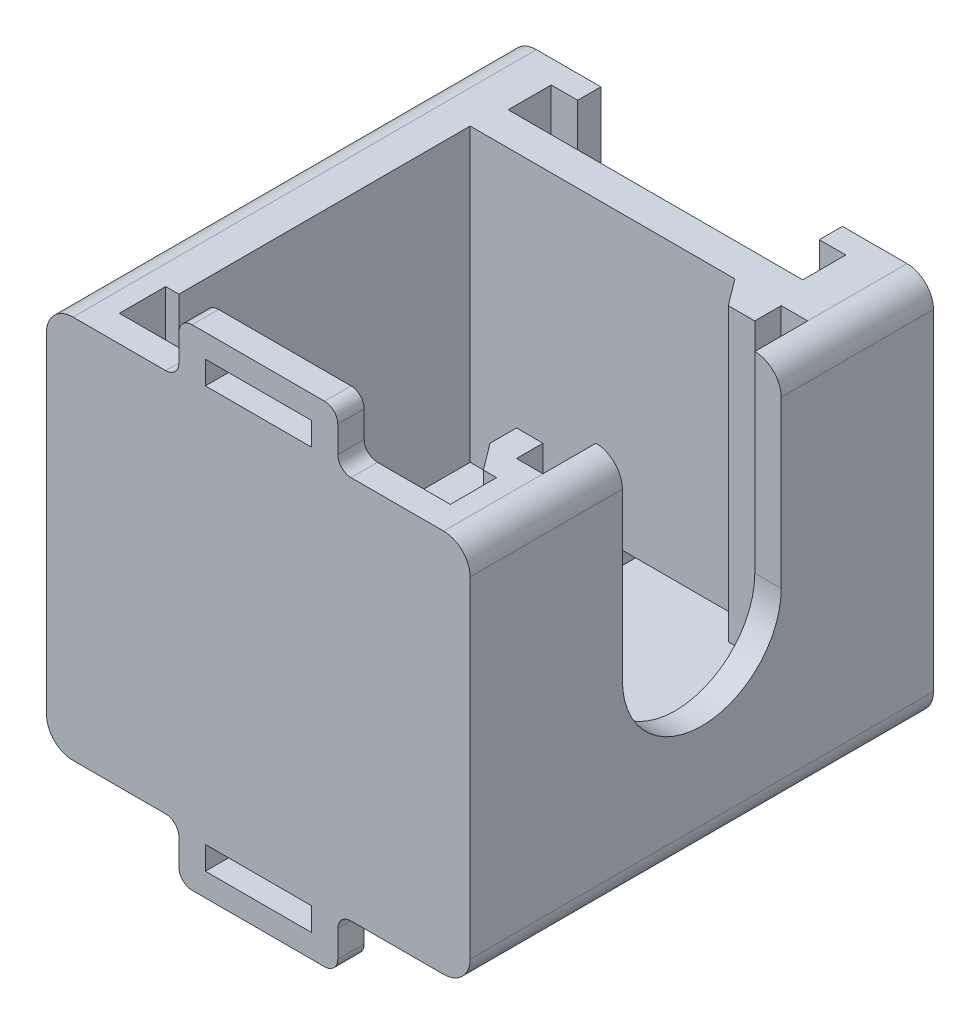
SolidWorks part; units mm, degrees
material "UNOBTANIUM"
ref_plane "Top Plane" through (0, 0, 0) normal (0, 0, 1) x (1, 0, 0)
ref_plane "Right Plane" through (0, 0, 0) normal (0, 1, 0) x (1, 0, 0)
ref_plane "Front Plane" through (0, 0, 0) normal (1, 0, 0) x (0, 0, -1)
ref_axis "x-axis" through (-17.6, 0, 0) along (1, 0, 0)
ref_axis "y-axis" through (0, -14.85, 0) along (0, 1, 0)
ref_axis "z-axis" through (0, 0, 36.75) along (0, 0, -1)
sketch "Sketch1" plane through (0, 0, 0) normal (0, 0, 1) x (1, 0, 0)
  line L1 (-16, 14.5) -> (16, 14.5)
  line L2 (-16, 14.5) -> (-16, -14.5)
  line L3 (-16, -14.5) -> (16, -14.5)
  line L4 (16, 14.5) -> (16, -14.5)
  line L5 (-16, 14.5) -> (16, -14.5) construction
  line L6 (-16, -14.5) -> (16, 14.5) construction
  point P0 (0, 0)
  dimension "D1" = 32
  dimension "D2" = 29
extrude "Boss-Extrude1" add sketch "Sketch1" along normal blind 35
fillet "Fillet1" radius 2 4 edges at (16, -14.5, 17.5) (16, 14.5, 17.5) (-16, -14.5, 17.5) (-16, 14.5, 17.5)
sketch "Sketch2" plane through (0, -14.5, 0) normal (0, -1, 0) x (1, 0, 0)
  line L0 (-9.125, 0) -> (-9.125, 1.75)
  line L1 (-14, 0) -> (14, 0) construction
  line L2 (-9.125, 1.75) -> (-11.125, 1.75)
  line L3 (-11.125, 1.75) -> (-11.125, 5)
  line L4 (-11.125, 5) -> (11.125, 5)
  line L5 (11.125, 5) -> (11.125, 1.75)
  line L6 (11.125, 1.75) -> (9.125, 1.75)
  line L7 (9.125, 1.75) -> (9.125, 0)
  line L9 (-9.125, 0) -> (9.125, 0)
  point P4 (0, 0)
  dimension "D1" = 18.25
  dimension "D2" = 1.75
  dimension "D3" = 3.25
  dimension "D4" = 22.25
extrude "Slot for Coil" cut sketch "Sketch2" against normal through all both and the other way through all
sketch "Sketch3" plane through (0, -14.5, 0) normal (0, -1, 0) x (1, 0, 0)
  line L0 (-9.125, 0) -> (-9.125, 1.75)
  line L1 (-9.125, 1.75) -> (-11.125, 1.75)
  line L2 (-11.125, 1.75) -> (-11.125, 5)
  line L3 (-11.125, 5) -> (11.125, 5)
  line L4 (11.125, 5) -> (11.125, 1.75)
  line L5 (11.125, 1.75) -> (9.125, 1.75)
  line L6 (9.125, 1.75) -> (9.125, 0)
  line L7 (9.125, 0) -> (-9.125, 0)
extrude "Boss-Extrude2" add sketch "Sketch3" against normal blind 7
sketch "Sketch4" plane through (0, 0, 1.75) normal (0, 0, -1) x (-1, 0, 0)
  line L1 (-9.125, 7.5) -> (-9.125, 6.5)
  line L2 (-9.125, 14.5) -> (-9.125, -7.5) construction
  arc A0 (-9.125, 7.5) -> (-9.125, 6.5) centre (-9.5, 7) cw
  dimension "D1" = 0.625
  dimension "D2" = 0.25
  dimension "D3" = 7
extrude "Boss-Extrude3" add sketch "Sketch4" along normal up to surface (1.75 mm away) up to face at (0, 1.1667, 0)
mirror "Mirror1" about plane through (0, 0, 0) normal (1, 0, 0) of "Boss-Extrude3"
sketch "Sketch5" plane through (0, 0, 0) normal (0, 0, -1) x (-1, 0, 0)
  line L0 (9.125, -7.5) -> (-9.125, -7.5) construction
  line L1 (-1, -7.5) -> (1, -7.5)
  line L2 (-1, -7.5) -> (-1, -14.5)
  line L3 (-1, -14.5) -> (1, -14.5)
  line L4 (1, -7.5) -> (1, -14.5)
  line L5 (14, -14.5) -> (-14, -14.5) construction
  point P8 (0, -7.5)
  dimension "D1" = 2
extrude "slot to feed in wire" cut sketch "Sketch5" against normal offset from surface (33 mm away) 2 up to face at (0, 0, 35)
sketch "Sketch6" plane through (0, 14.5, 0) normal (0, 1, 0) x (1, 0, 0)
  line L7 (11.5, -7.5) -> (-11.5, -7.5)
  line L8 (11.125, -5) -> (-11.125, -5) construction
  line L9 (0, -7.5) -> (0, -5) construction
  line L12 (-12.5, -33) -> (-12.5, -29.5)
  line L13 (-12.5, -29.5) -> (-11.5, -29.5)
  line L14 (-11.5, -29.5) -> (-11.5, -7.5)
  line L16 (12.5, -33) -> (12.5, -29.5)
  line L17 (12.5, -29.5) -> (11.5, -29.5)
  line L18 (11.5, -29.5) -> (11.5, -7.5)
  line L19 (-12.5, -33) -> (12.5, -33)
  line L20 (14, -35) -> (-14, -35) construction
  dimension "D1" = 2.5
  dimension "D2" = 3.5
  dimension "D3" = 1
  dimension "D4" = 23
  dimension "D5" = 2
  dimension "D6" = 3.5
  dimension "D7" = 1
extrude "slot fo PCB" cut sketch "Sketch6" against normal up to surface (22 mm away) up to face at (7.0833, -7.5, 2.25)
sketch "Sketch7" plane through (0, -14.5, 0) normal (0, -1, 0) x (1, 0, 0)
  line L0 (1, 0) -> (14, 0) construction
  line L1 (1, 0) -> (-1, 0)
  line L2 (1, 0) -> (1, 33)
  line L3 (1, 33) -> (-1, 33)
  line L4 (-1, 0) -> (-1, 33)
  line L5 (1, 33) -> (1, 0) construction
extrude "Boss-Extrude4" add sketch "Sketch7" against normal blind 0.25
fillet "Fillet2" radius 6 1 edges at (0, -14.25, 33)
ref_axis "Axis1" through (63.07, 0, 17.75) along (-1, 0, 0)
ref_plane "Plane1" through (0, 0, 17.75) normal (0, 0, -1) x (-1, 0, 0)
sketch "Sketch11" plane through (16, 0, 44) normal (1, 0, 0) x (0, 0, -1)
  line L0 (26.5, 25) -> (26.5, 0) construction
  line L4 (32.5, 25) -> (32.5, 0)
  line L5 (20.5, 25) -> (20.5, 0)
  line L6 (9, 12.5) -> (44, 12.5) construction
  line L7 (26.5, 0) -> (44, 0) construction
  line L8 (9, 12.5) -> (9, -12.5) construction
  arc A2 (32.5, 25) -> (20.5, 25) centre (26.5, 25) ccw
  arc A3 (20.5, 0) -> (32.5, 0) centre (26.5, 0) ccw
  point P2 (26.5, 12.5)
  dimension "D1" = 12
  dimension "D2" = 17.5
extrude "Rod Mount Slot" cut sketch "Sketch11" against normal up to next
sketch "Sketch14" plane through (0, 14.5, 0) normal (0, 1, 0) x (1, 0, 0)
  line L7 (14, -35) -> (14, -23.5) construction
  line L8 (11.5, -7.5) -> (14, -7.5)
  line L9 (11.5, -7.5) -> (11.5, -27.5)
  line L10 (11.5, -27.5) -> (14, -27.5)
  line L11 (14, -7.5) -> (14, -27.5)
  line L13 (12.5, -29.5) -> (11.5, -29.5) construction
  dimension "D2" = 2
extrude "Side cavity for mount plate" cut sketch "Sketch14" against normal up to surface (22 mm away) up to face at (-8.3333, -7.5, 23.3333)
sketch "Sketch16" plane through (0, 14.5, 0) normal (0, 1, 0) x (1, 0, 0)
  line L0 (1, -7.5) -> (14, -7.5) construction
  line L12 (12, -7.5) -> (10, -7.5)
  line L15 (12, -7.5) -> (12, -9.5)
  line L16 (12, -9.5) -> (10, -9.5)
  line L17 (10, -7.5) -> (10, -9.5)
  line L18 (14, -11.5) -> (14, -7.5) construction
  line L19 (14, -27.5) -> (11.5, -27.5) construction
  line L20 (12, -27.5) -> (10, -27.5)
  line L21 (12, -27.5) -> (12, -25.5)
  line L22 (12, -25.5) -> (10, -25.5)
  line L23 (10, -27.5) -> (10, -25.5)
  line L24 (14, -27.5) -> (14, -23.5) construction
  line L25 (14, -7.5) -> (14, -27.5) construction
  dimension "D6" = 2
  dimension "D7" = 2
  dimension "D8" = 2
  dimension "D9" = 2
  dimension "D10" = 4
extrude "Side stops for mount plate" add sketch "Sketch16" against normal up to surface (22 mm away) up to face at (-8.3333, -7.5, 23.3333)
sketch "Sketch20" plane through (0, 14.5, 0) normal (0, 1, 0) x (1, 0, 0)
  line L7 (11.5, -29.5) -> (10, -27.5)
  line L8 (10, -27.5) -> (11.5, -27.5)
  line L9 (11.5, -27.5) -> (11.5, -29.5)
  line L10 (10, -9.5) -> (8.5, -7.5)
  line L11 (10, -7.5) -> (-11.5, -7.5) construction
  line L12 (8.5, -7.5) -> (10, -7.5)
  line L13 (10, -7.5) -> (10, -9.5)
extrude "Boss-Extrude6" add sketch "Sketch20" against normal up to surface (22 mm away) up to face at (-8.3333, -7.5, 23.3333)
sketch "Sketch21" plane through (0, 14.5, 0) normal (0, 1, 0) x (-1, 0, 0)
  line L0 (0, 0) -> (0, 35) construction
  line L1 (-14, 35) -> (14, 35) construction
  line L2 (12.5, 33) -> (-12.5, 33) construction
  line L3 (-6, 35) -> (6, 35)
  line L4 (-6, 35) -> (-6, 33)
  line L5 (-6, 33) -> (6, 33)
  line L6 (6, 35) -> (6, 33)
  point P12 (0, 35)
  dimension "D1" = 12
extrude "Boss-Extrude7" add sketch "Sketch21" along normal blind 4
sketch "Sketch23" plane through (0, 0, 35) normal (0, 0, 1) x (1, 0, 0)
  line L0 (0, 0) -> (0, 18.5) construction
  line L1 (-6, 14.5) -> (-14, 14.5) construction
  line L3 (-4, 16.75) -> (4, 16.75)
  line L4 (-4, 16.75) -> (-4, 15)
  line L5 (-4, 15) -> (4, 15)
  line L6 (4, 16.75) -> (4, 15)
  line L7 (-6, 18.5) -> (6, 18.5) construction
  point P3 (0, 16.75)
  dimension "D1" = 1.75
  dimension "D2" = 8
  dimension "D3" = 0.5
extrude "Cut-Extrude7" cut sketch "Sketch23" against normal up to next
mirror "Mirror3" about plane through (0, 0, 0) normal (0, 1, 0) of "Boss-Extrude7", "Cut-Extrude7"
fillet "Fillet3" radius 1 8 edges at (-6, 14.5, 34) (6, 14.5, 34) (6, 18.5, 34) (-6, 18.5, 34) (6, -14.5, 34) (-6, -14.5, 34) (6, -18.5, 34) (-6, -18.5, 34)
sketch "Sketch26" plane through (-16, 0, 0) normal (1, 0, 0) x (0, 0, -1)
  circle A0 centre (-23.015, -2.89) radius 5.5
  point P2 (-25.005, -2.89)
  point P3 (-23.015, -2.89)
  dimension "D1" = 11
extrude "Cut-Extrude8" cut sketch "Sketch26" along normal up to next
